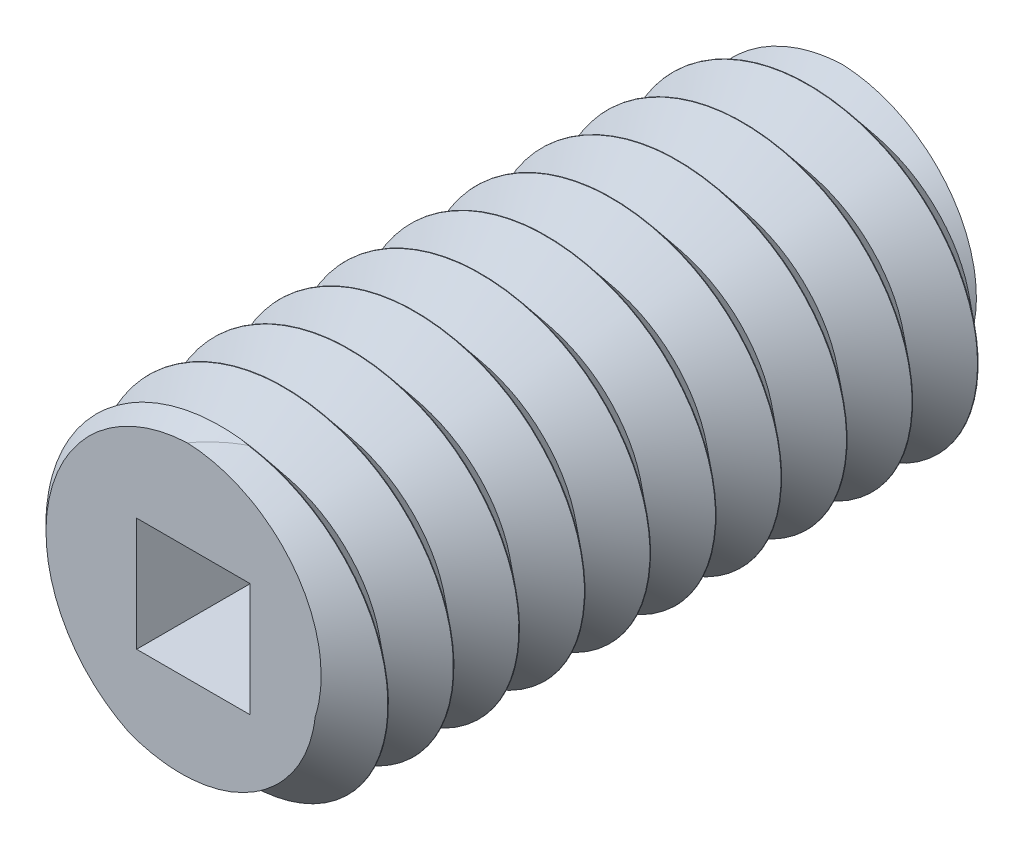
SolidWorks part; units mm, degrees
note: '?' marks a value the reader was unsure of.
ref_plane "Front Plane" through (0, 0, 0) normal (0, 0, 1) x (1, 0, 0)
ref_plane "Top Plane" through (0, 0, 0) normal (0, 1, 0) x (1, 0, 0)
ref_plane "Right Plane" through (0, 0, 0) normal (1, 0, 0) x (0, 0, -1)
sketch "Sketch1" plane through (0, 0, 0) normal (0, 0, 1) x (1, 0, 0)
  circle A0 centre (0, 0) radius 3
  dimension "D1" = 6
extrude "Boss-Extrude1" add sketch "Sketch1" along normal blind 12
sketch "Sketch2" plane through (0, 0, 0) normal (0, 0, -1) x (-1, 0, 0)
  circle A0 centre (0, 0) radius 3
  circle A2 centre (0, 0) radius 3 construction
curve "Helix/Spiral1" pitch 1.2 height 35 turns 29.1667
chamfer "Chamfer1" distance 0.3 angle 45 2 edges at (3, 0, 0) (3, 0, 12)
sketch "Sketch3" plane through (0, 0, 0) normal (1, 0, 0) x (0, 0, -1)
  line L0 (-0.3346, -3) -> (0.8554, -3)
  line L1 (0.8554, -3) -> (0.2604, -2.28)
  line L2 (0.2604, -2.28) -> (-0.3346, -3)
  line L3 (-0.3, -3) -> (-11.7, -3) construction
  dimension "D2" = 0.72
  dimension "D1" = 1.19
sweep "Cut-Sweep3" cut profiles "Sketch3" path "Helix/Spiral1"
sketch "Sketch4" plane through (0, 0, 0) normal (0, 0, -1) x (-1, 0, 0)
  line L0 (-1.04, -1.04) -> (-1.04, 1.04)
  line L7 (-1.04, 1.04) -> (1.04, 1.04)
  line L8 (1.04, 1.04) -> (1.04, -1.04)
  line L9 (-1.04, -1.04) -> (1.04, -1.04)
  point P4 (-1.04, 0)
  point P5 (0, 1.04)
  dimension "D2" = 2.08
extrude "Cut-Extrude1" cut sketch "Sketch4" against normal blind 5.5 draft 2
ref_plane "Plane1" through (0, 0, 6) normal (0, 0, -1) x (-1, 0, 0)
mirror "Mirror1" about plane through (0, 0, 6) normal (0, 0, -1) of "Cut-Extrude1"
ref_axis "Axis1" through (0, 0, -1.8529) along (0, 0, 1)?
equation "\"cleatShaftLen\" = 3"
equation "\"cleatHeadLen\" = 4mm"
equation "\"cleatHeadGirth\" = 12mm"
equation "\"cleatShaftGirth\" = 8mm"
equation "\"cleatTolOffset\" = 0.4mm"
equation "\"cleatCham\" = 1mm"
equation "\"cleatSpacing\" = 30mm"
equation "\"cleatTriangleAngle\" = 25deg"
equation "\"cleatMinimumTriangleAngle\" = 12deg"
equation "\"nCleats\" = 2"
equation "\"threadID\" = 8.3mm"
equation "\"threadPitch\" = 2mm"
equation "\"threadOD\" = 10.7mm"
equation "\"cleatFemShaftLen\" = \"cleatShaftLen\" - \"cleatTolOffset\""
equation "\"cleatFemHeadLen\" = \"cleatHeadLen\" + \"cleatTolOffset\" * 1.25"
equation "\"cleatFemHeadGirth\" = \"cleatHeadGirth\" + \"cleatTolOffset\""
equation "\"cleatFemShaftGirth\" = \"cleatShaftGirth\" + \"cleatTolOffset\""
equation "\"lip\" = 2mm"
equation "\"cubeCham\" = 0.7mm"
equation "\"cubeCutoutPadding\" = 3mm"
equation "\"wall\" = 3mm"
equation "\"cleatLen\" = \"cleatShaftLen\" + \"cleatHeadLen\""
equation "\"coverThickness\" = 2mm"
equation "\"plugDepth\" = 4mm"
equation "\"bottomChamOffset\" = 1.8mm"
equation "\"maleHelperAngle\" = 45deg"
equation "\"maleHelperAngle2\" = 35deg"
equation "\"stFactor\" = 0.6"
equation "\"stID\" = \"threadID\" * \"stFactor\""
equation "\"stOD\" = \"threadOD\" * \"stFactor\""
equation "\"stPitch\" = \"threadPitch\" * \"stFactor\""
equation "\"temp\" = 0"
equation "\"threadMaleOD\" = 10.0mm"
equation "\"stMaleOD\" = \"threadMaleOD\" * \"stFactor\""
equation "\"D1@Sketch1\"=\"stMaleOD\""
equation "\"D1@Boss-Extrude1\"=12mm"
equation "\"D2@Sketch3\"=(\"stOD\"-\"stID\")/2"
equation "\"D1@Sketch3\"=\"stPitch\"-0.01"
equation "\"stProtrusion\" = (\"stOD\" - \"stID\") / 2"
equation "\"stHexDiam\" = 2.5mm"
equation "\"stHexPad\" = 0.08mm"
equation "\"stSocketHeadProtrusion\" = 0.65mm"
equation "\"stSocketHeadLen\" = 1.2mm"
equation "\"stSocketHeadLenPad\" = 0.1mm"
equation "\"stSocketHeadCounterboreDepth\" = \"stSocketHeadLen\" + \"stSocketHeadLenPad\""
equation "\"stDriverDepth\" = 2mm"
equation "\"stNutODPad\" = 3mm"
equation "\"stNutDiam\" = \"stOD\" + \"stNutODPad\""
equation "\"stNutHeight\" = 3mm"
equation "\"stNutCham\" = 0.4mm"
equation "\"stSocketHeadDiam\" = \"stOD\" + \"stSocketHeadProtrusion\""
